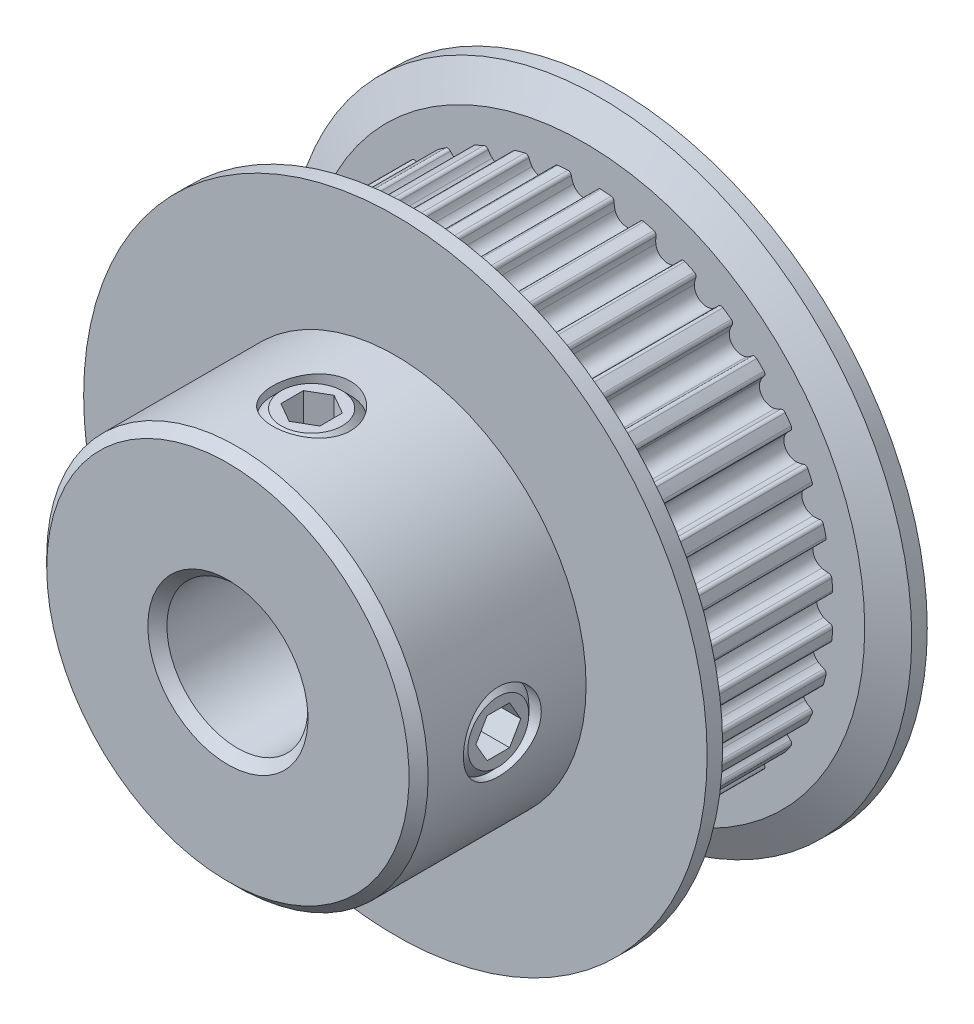
SolidWorks part; units mm, degrees
ref_plane "Front Plane" through (0, 0, 0) normal (0, 0, 1) x (1, 0, 0)
ref_plane "Top Plane" through (0, 0, 0) normal (0, 1, 0) x (1, 0, 0)
ref_plane "Right Plane" through (0, 0, 0) normal (1, 0, 0) x (0, 0, -1)
sketch "Sketch1" plane through (0, 0, 0) normal (0, 0, 1) x (1, 0, 0)
  line L1 (-1.8459, 10.4515) -> (1.8459, 10.4515) construction
  line L4 (0, 0) -> (0, 10.4515) construction
  line L5 (0, 10.4515) -> (0, 14.6793) construction
  line L6 (0, 11.4555) -> (1.9924, 11.2809) construction
  line L7 (1.9924, 11.2809) -> (2.8218, 11.1344) construction
  line L8 (1.9924, 11.2809) -> (1.8459, 10.4515) construction
  line L9 (-1.9924, 11.2809) -> (-1.8459, 10.4515) construction
  line L10 (-1.9482, 11.0308) -> (-2.4785, 14.0335)
  line L11 (-2.4785, 14.0335) -> (2.4785, 14.0335)
  line L12 (2.4785, 14.0335) -> (1.9482, 11.0308)
  circle A0 centre (0, 0) radius 11.4555 construction
  circle A1 centre (0, 0) radius 14.0335 construction
  circle A2 centre (0, 0) radius 11.2015 construction
  arc A3 (-0.4989, 10.7633) -> (0.4989, 10.7633) centre (0, 11.0065) ccw
  arc A4 (-0.4989, 10.7633) -> (-0.5884, 11.0497) centre (0.4, 11.2015) cw
  arc A5 (-1.9482, 11.0308) -> (-0.7467, 11.1766) centre (0, 0) cw
  arc A6 (-0.5884, 11.0497) -> (-0.7467, 11.1766) centre (-0.7367, 11.0269) ccw
  arc A7 (1.9482, 11.0308) -> (0.7467, 11.1766) centre (0, 0) ccw
  arc A8 (0.5884, 11.0497) -> (0.7467, 11.1766) centre (0.7367, 11.0269) cw
  arc A9 (0.4989, 10.7633) -> (0.5884, 11.0497) centre (-0.4, 11.2015) ccw
  point P6 (0, 20.9083)
  point P11 (0, 11.4555)
  point P13 (0, 14.0335)
  point P14 (0, 11.2015)
  dimension "D1" = 6.2291
  dimension "D2" = 3.2238
sketch "Sketch2" plane through (0, 0, 0) normal (1, 0, 0) x (0, 0, -1)
  line L0 (-8.7249, 3.175) -> (8.7249, 3.175)
  line L1 (-8.7249, 3.175) -> (-8.7249, 8.585)
  line L2 (-8.7249, 8.585) -> (-1.1851, 8.585)
  line L3 (-1.1851, 8.585) -> (-1.1851, 14.0335)
  line L4 (-1.1851, 14.0335) -> (0.2149, 14.0335) construction
  line L5 (0.2149, 14.0335) -> (0.2149, 11.2015) construction
  line L6 (0.2149, 11.2015) -> (7.3249, 11.2015)
  line L7 (7.3249, 11.2015) -> (7.3249, 14.0335) construction
  line L8 (7.3249, 14.0335) -> (8.7249, 14.0335) construction
  line L9 (8.7249, 14.0335) -> (8.7249, 3.175)
  line L10 (-8.7249, 0) -> (8.7249, 0) construction
  line L11 (8.0249, 14.0335) -> (7.3249, 12.6175)
  line L12 (0.2149, 12.6175) -> (-0.4851, 14.0335)
  line L13 (-1.1851, 14.0335) -> (-0.4851, 14.0335)
  line L14 (0.2149, 12.6175) -> (0.2149, 11.2015)
  line L15 (7.3249, 11.2015) -> (7.3249, 12.6175)
  line L16 (8.0249, 14.0335) -> (8.7249, 14.0335)
  arc A0 (0.2149, 12.6175) -> (-0.4851, 14.0335) centre (-1.5673, 12.6175) ccw construction
  arc A1 (7.3249, 12.6175) -> (8.0249, 14.0335) centre (9.1071, 12.6175) cw construction
  point P12 (0.2149, 12.6175)
  point P14 (-0.4851, 14.0335)
  point P20 (7.3249, 12.6175)
  point P21 (8.0249, 14.0335)
  point P25 (7.3249, 0)
  point P26 (0.2149, 0)
revolve "Revolve1" add sketch "Sketch2" angle 360 mid plane about L10
sketch "Sketch3" plane through (0, 0, 0) normal (0, 0, 1) x (1, 0, 0)
  line L6 (2.4785, 14.0335) -> (-2.4785, 14.0335)
  line L7 (1.9482, 11.0308) -> (2.4785, 14.0335)
  line L8 (-2.4785, 14.0335) -> (-1.9482, 11.0308)
  line L9 (2.4785, 14.0335) -> (-2.4785, 14.0335)
  line L10 (1.9482, 11.0308) -> (2.4785, 14.0335)
  line L11 (-2.4785, 14.0335) -> (-1.9482, 11.0308)
  arc A8 (1.9482, 11.0308) -> (0.7467, 11.1766) centre (0, 0) ccw
  arc A9 (0.7467, 11.1766) -> (0.5884, 11.0497) centre (0.7367, 11.0269) ccw
  arc A10 (0.4989, 10.7633) -> (0.5884, 11.0497) centre (-0.4, 11.2015) ccw
  arc A11 (-0.4989, 10.7633) -> (0.4989, 10.7633) centre (0, 11.0065) ccw
  arc A12 (-0.5884, 11.0497) -> (-0.4989, 10.7633) centre (0.4, 11.2015) ccw
  arc A13 (-0.5884, 11.0497) -> (-0.7467, 11.1766) centre (-0.7367, 11.0269) ccw
  arc A14 (-0.7467, 11.1766) -> (-1.9482, 11.0308) centre (0, 0) ccw
  arc A15 (1.9482, 11.0308) -> (0.7467, 11.1766) centre (0, 0) ccw
  arc A16 (0.7467, 11.1766) -> (0.5884, 11.0497) centre (0.7367, 11.0269) ccw
  arc A17 (0.4989, 10.7633) -> (0.5884, 11.0497) centre (-0.4, 11.2015) ccw
  arc A18 (-0.4989, 10.7633) -> (0.4989, 10.7633) centre (0, 11.0065) ccw
  arc A19 (-0.5884, 11.0497) -> (-0.4989, 10.7633) centre (0.4, 11.2015) ccw
  arc A20 (-0.5884, 11.0497) -> (-0.7467, 11.1766) centre (-0.7367, 11.0269) ccw
  arc A21 (-0.7467, 11.1766) -> (-1.9482, 11.0308) centre (0, 0) ccw
  dimension "D1" = 0
extrude "Cut-Extrude1" cut sketch "Sketch3" against normal up to vertex (7.3249 mm away) from vertex up to point (0, 11.2015, -7.3249) starting at point (0, 11.2015, -0.2149)
pattern_circular "CirPattern1" count 36 over 360 about axis through (0, 0, 8.7249) along (0, 0, 1) of "Cut-Extrude1"
sketch "Sketch4" plane through (0, 0, 0) normal (1, 0, 0) x (0, -1, 0)
  line L0 (0, -1.1851) -> (0, -8.7249) construction
  line L1 (-8.585, -1.1851) -> (8.585, -1.1851) construction
  line L2 (-8.585, -8.7249) -> (8.585, -8.7249) construction
  circle A0 centre (0, -4.955) radius 1.7526
extrude "Cut-Extrude2" cut sketch "Sketch4" along normal through all
ref_plane "Plane1" through (0, 0, 4.955) normal (0, 0, 1) x (1, 0, 0)
sketch "Sketch5" plane through (0, 0, 4.955) normal (0, 0, 1) x (1, 0, 0)
  line L0 (0, 0.1664) -> (0, 8.585) construction
  line L1 (3.175, -1.3716) -> (3.175, 0)
  line L2 (3.556, -1.7526) -> (8.0232, -1.7526)
  line L3 (3.175, 0) -> (8.585, 0) construction
  line L4 (3.175, 0) -> (8.4042, 0)
  line L5 (8.4042, 0) -> (8.4042, -1.3716)
  line L6 (3.556, -1.7526) -> (3.175, -1.3716)
  line L7 (8.4042, -1.3716) -> (8.0232, -1.7526)
  circle A0 centre (0, 0) radius 8.585 construction
  circle A1 centre (0, 0) radius 3.175 construction
  point P2 (3.175, -1.7526)
  point P11 (8.4042, -1.7526)
revolve "Revolve2" add sketch "Sketch5" angle 360 mid plane about L4
sketch "Sketch6" plane through (8.4042, 5.3841, 0) normal (-1, 0, 0) x (0, -1, 0)
  line L1 (5.3841, 5.9669) -> (4.5078, 5.4609)
  line L2 (4.5078, 5.4609) -> (4.5078, 4.4491)
  line L3 (4.5078, 4.4491) -> (5.3841, 3.9431)
  line L4 (5.3841, 3.9431) -> (6.2604, 4.4491)
  line L5 (6.2604, 4.4491) -> (6.2604, 5.4609)
  line L6 (6.2604, 5.4609) -> (5.3841, 5.9669)
  circle A0 centre (5.3841, 4.955) radius 0.8763 construction
  dimension "D1" = 1.7526
extrude "Cut-Extrude3" cut sketch "Sketch6" along normal blind 1.3144
pattern_circular "CirPattern2" count 2 over 90 about axis through (0, 0, 8.7249) along (0, 0, 1) of "Cut-Extrude2", "Revolve2", "Cut-Extrude3"
chamfer "Chamfer1" distance 0.4293 angle 45 2 edges at (3.175, 0, 8.7249) (8.585, 0, 8.7249)
ref_axis "Center Axis 1" through (0, 0, -8.7249) along (0, 0, 1)
ref_plane "Contact Plane 1" through (0, 0, 8.7249) normal (0, 0, 1) x (1, 0, 0)
ref_plane "Contact Plane 2" through (0, 0, -8.7249) normal (0, 0, -1) x (-1, 0, 0)
equation "\"D2@Sketch1\" = \"D1@Sketch1\"/2"
equation "\"D1@Sketch6\" = \"Set Screw@Sketch4\" / 2"
equation "\"D1@Cut-Extrude3\" = \"D1@Sketch6\"*.75"
equation "\"D1@Chamfer1\"=\"Hub Dia@Sketch2\"*.025"
